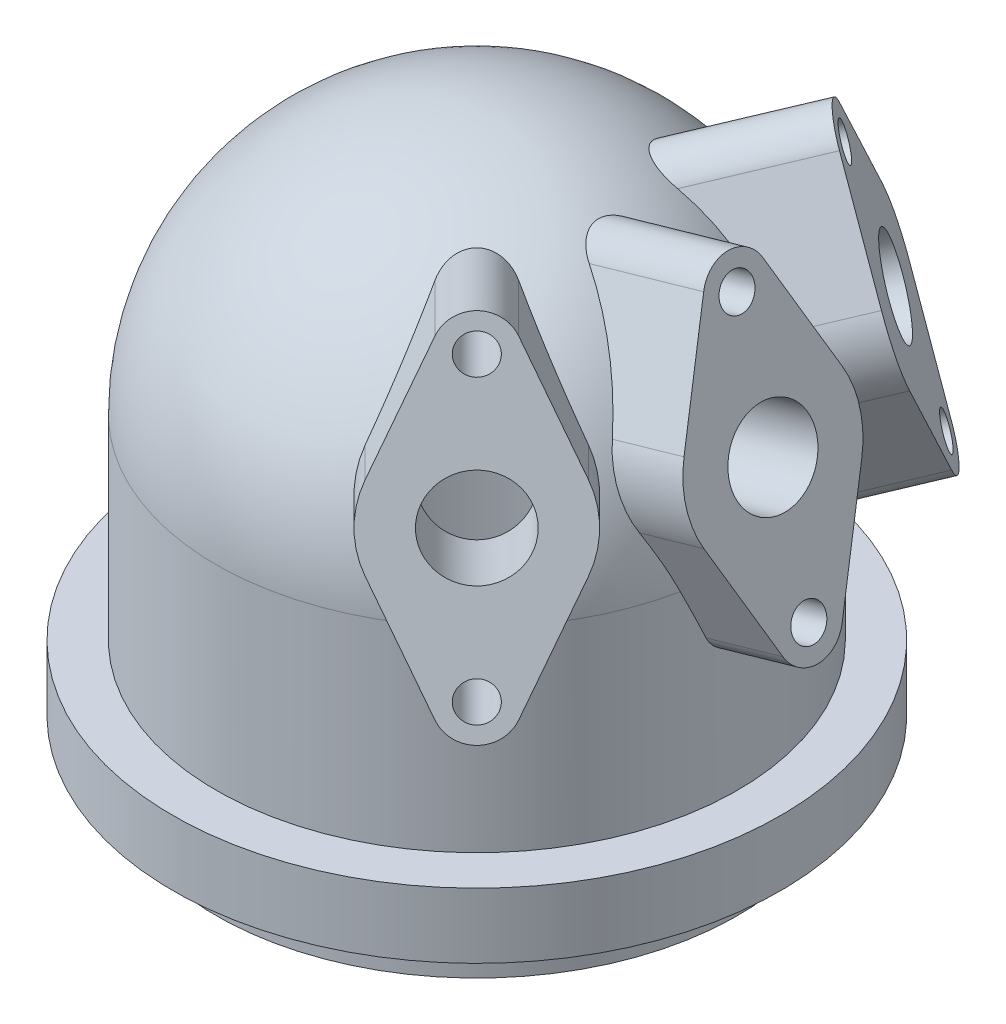
SolidWorks part; units mm, degrees
ref_plane "Front Plane" through (0, 0, 0) normal (0, 0, 1) x (1, 0, 0)
ref_plane "Top Plane" through (0, 0, 0) normal (0, 1, 0) x (1, 0, 0)
ref_plane "Right Plane" through (0, 0, 0) normal (1, 0, 0) x (0, 0, -1)
sketch "Sketch1" plane through (0, 0, 0) normal (0, 0, 1) x (1, 0, 0)
  line L8 (-50, 0) -> (-50, 70)
  line L9 (-60, 0) -> (-60, 10)
  line L10 (-60, 0) -> (-50, 0)
  line L11 (0, 120) -> (0, 130)
  line L12 (-60, 25) -> (-70, 25)
  line L13 (-70, 25) -> (-70, 10)
  line L14 (-70, 10) -> (-60, 10)
  line L15 (-60, 25) -> (-60, 70)
  line L16 (-60, 0) -> (-60, 70) construction
  line L17 (0, 0) -> (0, 54.4278) construction
  arc A2 (-50, 70) -> (0, 120) centre (0, 70) cw
  arc A3 (-60, 70) -> (0, 130) centre (0, 70) cw
  dimension "D5" = 50
  dimension "D1" = 10
  dimension "D2" = 10
  dimension "D3" = 15
  dimension "D4" = 130
  dimension "D6" = 70
revolve "Revolve1" add sketch "Sketch1" angle 360 about L17
sketch "Sketch2" plane through (0, 0, 0) normal (0, 0, 1) x (1, 0, 0)
  line L0 (0, 76) -> (68.1919, 95.5537)
  line L2 (0, 76) -> (94.8829, 76) construction
  point P2 (0, 0)
  point P3 (0, 76)
  point P4 (0, 0)
  dimension "D1" = 16
  dimension "D2" = 70.94
  dimension "D3" = 76
ref_plane "Plane1" through (68.1919, 95.5537, 0) normal (0.9613, 0.2756, 0) x (0, 0, -1)
sketch "Sketch4" plane through (68.1919, 95.5537, 0) normal (0.9613, 0.2756, 0) x (0, 0, -1)
  line L0 (0, 0) -> (0, -26.1533) construction
  line L1 (0, 0) -> (75.6994, 0) construction
  line L2 (-18.1812, 8.3333) -> (-6.8179, 33.125)
  line L3 (0, -1.5559) -> (0, -144.5559) construction
  line L4 (18.1812, 8.3333) -> (6.8179, 33.125)
  line L5 (18.1812, -8.3333) -> (6.8179, -33.125)
  line L6 (-18.1812, -8.3333) -> (-6.8179, -33.125)
  arc A0 (-18.1812, 8.3333) -> (-18.1812, -8.3333) centre (0, 0) ccw
  arc A1 (6.8179, 33.125) -> (-6.8179, 33.125) centre (0, 30) ccw
  arc A2 (6.8179, -33.125) -> (-6.8179, -33.125) centre (0, -30) cw
  arc A3 (18.1812, -8.3333) -> (18.1812, 8.3333) centre (0, 0) ccw
  point P1 (-34.0984, -7.1836)
  point P6 (0, 0)
  dimension "D1" = 40
  dimension "D2" = 15
  dimension "D3" = 60
  dimension "D4" = 30
extrude "Boss-Extrude1" add sketch "Sketch4" against normal up to next
pattern_circular "CirPattern1" count 2 every 45 about axis through (0, 0, 0) along (0, -1, 0) of "Boss-Extrude1" other way count 2
hole_wizard "Hole1" positions "Sketch5" profile "Sketch6" legacy end condition up to next
sketch "Sketch5" plane through (62.4579, 25.3279, 62.4579) normal (0.6797, 0.2756, 0.6797) x (0.7335, -0.2554, -0.6299)
  point P0 (-27.3848, 99.3508)
  point P3 (-11.4411, 41.5079)
sketch "Sketch6" plane through (42.3718, 124.3916, 42.3718) normal (0.5015, 0.5015, -0.7049) x (0.5352, -0.8201, -0.2027)
  line L0 (0, 0) -> (0, 37.6556)
  line L1 (0, 37.6556) -> (4, 37.6556)
  line L2 (4, 37.6556) -> (4, 0)
  line L3 (4, 0) -> (0, 0)
  line L4 (0, 110) -> (0, -10) construction
  dimension "Diameter" = 8
  dimension "Depth" = 37.6556
hole_wizard "Hole2" positions "Sketch7" profile "Sketch8" legacy end condition up to next
sketch "Sketch7" plane through (88.3288, 25.3279, 0) normal (0.9613, 0.2756, 0) x (0, 0, -1)
  point P0 (0, 103.0559)
  point P3 (0, 43.0559)
sketch "Sketch8" plane through (59.9228, 124.3916, 0) normal (0, 0, 1) x (-0.2756, 0.9613, 0)
  line L0 (0, 0) -> (0, 37.6556)
  line L1 (0, 37.6556) -> (4, 37.6556)
  line L2 (4, 37.6556) -> (4, 0)
  line L3 (4, 0) -> (0, 0)
  line L4 (0, 110) -> (0, -10) construction
  dimension "Diameter" = 8
  dimension "Depth" = 37.6556
hole_wizard "Hole3" positions "Sketch9" profile "Sketch10" legacy end condition up to next
sketch "Sketch9" plane through (62.4579, 25.3279, -62.4579) normal (0.6797, 0.2756, -0.6797) x (-0.7335, 0.2554, -0.6299)
  point P0 (27.3848, 99.3508)
  point P3 (11.4411, 41.5079)
sketch "Sketch10" plane through (42.3718, 124.3916, -42.3718) normal (0.5015, 0.5015, 0.7049) x (-0.5352, 0.8201, -0.2027)
  line L0 (0, 0) -> (0, 37.6556)
  line L1 (0, 37.6556) -> (4, 37.6556)
  line L2 (4, 37.6556) -> (4, 0)
  line L3 (4, 0) -> (0, 0)
  line L4 (0, 110) -> (0, -10) construction
  dimension "Diameter" = 8
  dimension "Depth" = 37.6556
hole_wizard "Hole4" positions "Sketch11" profile "Sketch12" legacy end condition up to next
sketch "Sketch11" plane through (88.3288, 25.3279, 0) normal (0.9613, 0.2756, 0) x (0, 0, -1)
  point P0 (0, 73.0559)
sketch "Sketch12" plane through (68.1919, 95.5537, 0) normal (0, 0, 1) x (-0.2756, 0.9613, 0)
  line L0 (0, 0) -> (0, 22.9276)
  line L1 (0, 22.9276) -> (10, 22.9276)
  line L2 (10, 22.9276) -> (10, 0)
  line L3 (10, 0) -> (0, 0)
  line L4 (0, 110) -> (0, -10) construction
  dimension "Diameter" = 20
  dimension "Depth" = 22.9276
hole_wizard "Hole5" positions "Sketch13" profile "Sketch14" legacy end condition up to next
sketch "Sketch13" plane through (62.4579, 25.3279, 62.4579) normal (0.6797, 0.2756, 0.6797) x (0.7335, -0.2554, -0.6299)
  point P0 (-19.413, 70.4294)
sketch "Sketch14" plane through (48.219, 95.5537, 48.219) normal (0.5015, 0.5015, -0.7049) x (0.5352, -0.8201, -0.2027)
  line L0 (0, 0) -> (0, 22.9276)
  line L1 (0, 22.9276) -> (10, 22.9276)
  line L2 (10, 22.9276) -> (10, 0)
  line L3 (10, 0) -> (0, 0)
  line L4 (0, 110) -> (0, -10) construction
  dimension "Diameter" = 20
  dimension "Depth" = 22.9276
hole_wizard "Hole6" positions "Sketch15" profile "Sketch16" legacy end condition up to next
sketch "Sketch15" plane through (62.4579, 25.3279, -62.4579) normal (0.6797, 0.2756, -0.6797) x (-0.7335, 0.2554, -0.6299)
  point P0 (19.413, 70.4294)
sketch "Sketch16" plane through (48.219, 95.5537, -48.219) normal (0.5015, 0.5015, 0.7049) x (-0.5352, 0.8201, -0.2027)
  line L0 (0, 0) -> (0, 22.9276)
  line L1 (0, 22.9276) -> (10, 22.9276)
  line L2 (10, 22.9276) -> (10, 0)
  line L3 (10, 0) -> (0, 0)
  line L4 (0, 110) -> (0, -10) construction
  dimension "Diameter" = 20
  dimension "Depth" = 22.9276
